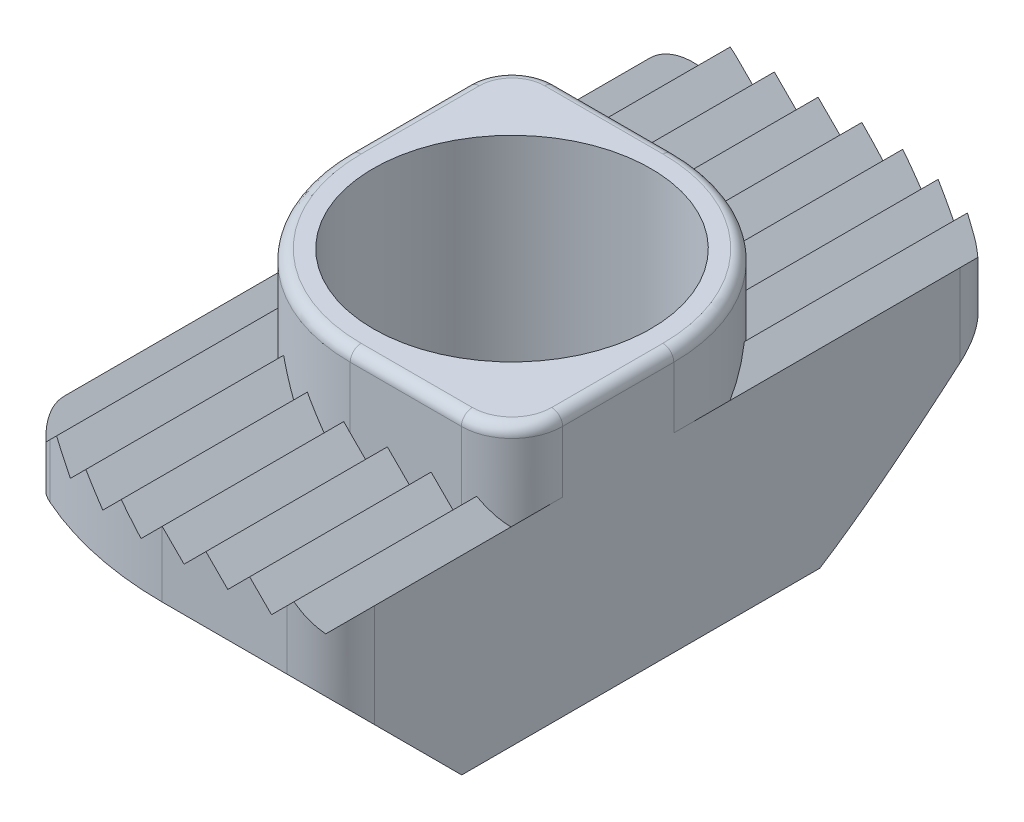
SolidWorks part; units mm, degrees
material "AISI 1020"
ref_plane "Front Plane" through (0, 0, 0) normal (0, 0, 1) x (1, 0, 0)
ref_plane "Top Plane" through (0, 0, 0) normal (0, 1, 0) x (1, 0, 0)
ref_plane "Right Plane" through (0, 0, 0) normal (1, 0, 0) x (0, 0, -1)
sketch "Sketch1" plane through (0, 0, 0) normal (0, 1, 0) x (1, 0, 0)
  line L0 (0, -8) -> (2.85, -8)
  line L1 (3.85, -7) -> (3.85, 6.3936)
  line L2 (0, 8) -> (-2.85, 8)
  line L3 (-3.85, 7) -> (-3.85, -6.3936)
  arc A0 (-3.85, -6.3936) -> (-3.2571, -7.3069) centre (-2.85, -6.3936) ccw
  arc A1 (-3.2571, -7.3069) -> (0, -8) centre (0, 0) ccw
  arc A2 (2.85, -8) -> (3.85, -7) centre (2.85, -7) ccw
  arc A3 (3.85, 6.3936) -> (3.2571, 7.3069) centre (2.85, 6.3936) ccw
  arc A4 (3.2571, 7.3069) -> (0, 8) centre (0, 0) ccw
  arc A5 (-2.85, 8) -> (-3.85, 7) centre (-2.85, 7) ccw
extrude "Extrude1" add sketch "Sketch1" along normal blind 4.5
sketch "Sketch2" plane through (0, 0, 0) normal (0, 0, 1) x (1, 0, 0)
  line L0 (-4, 4.5) -> (-3.5, 4)
  line L1 (-3.5, 4) -> (-3, 4.5)
  line L2 (-3, 4.5) -> (-2.5, 4)
  line L3 (-2.5, 4) -> (-2, 4.5)
  line L4 (-2, 4.5) -> (-1.5, 4)
  line L5 (-1.5, 4) -> (-1, 4.5)
  line L6 (-1, 4.5) -> (-0.5, 4)
  line L7 (-0.5, 4) -> (0, 4.5)
  line L8 (0, 4.5) -> (0.5, 4)
  line L9 (0.5, 4) -> (1, 4.5)
  line L10 (1, 4.5) -> (1.5, 4)
  line L11 (1.5, 4) -> (2, 4.5)
  line L12 (2, 4.5) -> (2.5, 4)
  line L13 (2.5, 4) -> (3, 4.5)
  line L14 (3, 4.5) -> (3.5, 4)
  line L15 (3.5, 4) -> (4, 4.5)
  line L16 (4, 4.5) -> (4, 5.5)
  line L17 (4, 5.5) -> (-4, 5.5)
  line L18 (-4, 5.5) -> (-4, 4.5)
extrude "Cut-Extrude1" cut sketch "Sketch2" against normal blind 8 and the other way blind 8
sketch "Sketch3" plane through (0, 0, 0) normal (0, 1, 0) x (1, 0, 0)
  line L0 (0.15, -3.85) -> (2.6933, -3.85)
  line L1 (3.85, -2.6933) -> (3.85, -0.15)
  line L2 (-0.15, 3.85) -> (-2.85, 3.85)
  line L3 (-3.85, 2.85) -> (-3.85, 0.15)
  arc A0 (-3.85, 0.15) -> (0.15, -3.85) centre (0.15, 0.15) ccw
  arc A1 (2.6933, -3.85) -> (3.85, -2.6933) centre (2.6933, -2.6933) ccw
  arc A2 (3.85, -0.15) -> (-0.15, 3.85) centre (-0.15, -0.15) ccw
  arc A3 (-2.85, 3.85) -> (-3.85, 2.85) centre (-2.85, 2.85) ccw
extrude "Extrude2" add sketch "Sketch3" along normal blind 6.0004
sketch "Sketch4" plane through (0, 0, 0) normal (1, 0, 0) x (0, 0, -1)
  line L0 (-9, -1) -> (9, -1)
  line L1 (9, -1) -> (9, 4)
  line L2 (9, 4) -> (5, 0)
  line L3 (5, 0) -> (-5, 0)
  line L4 (-5, 0) -> (-9, 4)
  line L5 (-9, 4) -> (-9, -1)
extrude "Cut-Extrude2" cut sketch "Sketch4" against normal blind 4 and the other way blind 4
sketch "Sketch5" plane through (0, 0, 0) normal (1, 0, 0) x (0, 0, -1)
  line L0 (0, -1) -> (-9, -1)
  line L1 (-9, -1) -> (-9, 3)
  line L2 (-9, 3) -> (-8, 3)
  line L3 (-8, 3) -> (-5, 0)
  line L4 (-5, 0) -> (0, 0)
  line L5 (0, 0) -> (0, -1)
  line L6 (0, 3) -> (0, -1) construction
revolve "Cut-Revolve1" cut sketch "Sketch5" angle 60 about L6
sketch "Sketch6" plane through (0, 0, 0) normal (1, 0, 0) x (0, 0, -1)
  line L0 (0, 0) -> (5, 0)
  line L1 (5, 0) -> (8, 3)
  line L2 (8, 3) -> (9, 3)
  line L3 (9, 3) -> (9, -1)
  line L4 (9, -1) -> (0, -1)
  line L5 (0, -1) -> (0, 0)
  line L6 (0, -1) -> (0, 3) construction
revolve "Cut-Revolve2" cut sketch "Sketch6" angle 60 about L6 reverse direction yes
sketch "Sketch9" plane through (0, 6.0004, 0) normal (0, 1, 0) x (1, 0, 0)
  circle A0 centre (0, 0) radius 2.4879
extrude "Cut-Extrude3" cut sketch "Sketch9" against normal through all
fillet "Fillet4" radius 0.25 8 edges at (3.5112, 6.0004, 3.5112) (1.4217, 6.0004, 3.85) (-2.6784, 6.0004, 2.6784) (-3.85, 6.0004, -1.5) (-3.5571, 6.0004, -3.5571) (-1.5, 6.0004, -3.85) (2.6784, 6.0004, -2.6784) (3.85, 6.0004, 1.4217)
sketch "Sketch10" plane through (0, 6.0004, 0) normal (0, 1, 0) x (1, 0, 0)
  circle A0 centre (0, 0) radius 2.4879
extrude "Extrude3" add sketch "Sketch10" against normal up to surface (6.0004 mm away) up to face at (0, 0, 2.4879)
sketch "Sketch12" plane through (0, 6.0004, 0) normal (0, 1, 0) x (1, 0, 0)
  circle A0 centre (0, 0) radius 3.175
  dimension "D1" = 6.35
extrude "Cut-Extrude4" cut sketch "Sketch12" against normal through all
